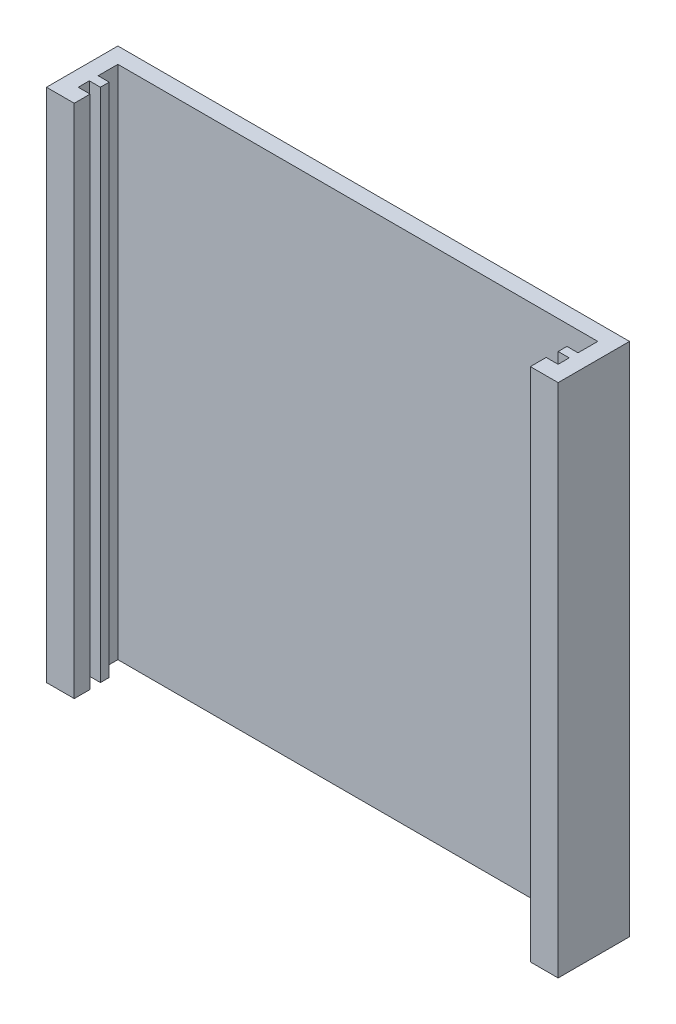
SolidWorks part; units mm, degrees
ref_plane "Front Plane" through (0, 0, 0) normal (0, 0, 1) x (1, 0, 0)
ref_plane "Top Plane" through (0, 0, 0) normal (0, 1, 0) x (1, 0, 0)
ref_plane "Right Plane" through (0, 0, 0) normal (1, 0, 0) x (0, 0, -1)
sketch "Sketch8" plane through (0, 0, 0) normal (0, 1, 0) x (1, 0, 0)
  line L0 (-2.6978, 0.4813) -> (56.8644, 0.4813)
  line L1 (56.8644, 0.4813) -> (56.8644, -2.0093)
  line L2 (56.8644, -2.0093) -> (55.4644, -2.0093)
  line L3 (55.4644, -2.0093) -> (55.4644, -3.1187)
  line L4 (55.4644, -3.1187) -> (56.8644, -3.1187)
  line L5 (56.8644, -3.1187) -> (56.8644, -4.5187)
  line L6 (56.8644, -4.5187) -> (55.3644, -4.5187)
  line L7 (55.3644, -4.5187) -> (55.3644, -6.5187)
  line L8 (55.3644, -6.5187) -> (58.8644, -6.5187)
  line L9 (58.8644, -6.5187) -> (58.8644, 2.4813)
  line L10 (58.8644, 2.4813) -> (-5.6356, 2.4813)
  line L11 (-5.6356, 2.4813) -> (-5.6356, -6.5187)
  line L12 (-5.6356, -6.5187) -> (-2.1356, -6.5187)
  line L13 (-2.1356, -6.5187) -> (-2.1356, -4.5187)
  line L14 (-2.1356, -4.5187) -> (-3.6356, -4.5187)
  line L15 (-3.6356, -4.5187) -> (-3.6356, -3.1187)
  line L16 (-3.6356, -3.1187) -> (-2.2356, -3.1187)
  line L17 (-2.2356, -3.1187) -> (-2.2356, -2.0093)
  line L18 (-2.2356, -2.0093) -> (-3.6356, -2.0093)
  line L19 (-3.6356, -2.0093) -> (-3.6356, 0.4813)
  line L20 (-3.6356, 0.4813) -> (-2.6978, 0.4813)
  point P2 (-3.6356, -3.8187)
  dimension "D1" = 1.4
  dimension "D2" = 1.4
  dimension "D3" = 1.5
  dimension "D4" = 1.5
  dimension "D5" = 1.4
  dimension "D6" = 1.4
  dimension "D7" = 2
  dimension "D8" = 2
  dimension "D9" = 2
  dimension "D10" = 2
  dimension "D11" = 2
  dimension "D12" = 2
  dimension "D13" = 2
  dimension "D14" = 9
  dimension "D15" = 9
  dimension "D16" = 64.5
extrude "Boss-Extrude1" add sketch "Sketch8" along normal blind 65
